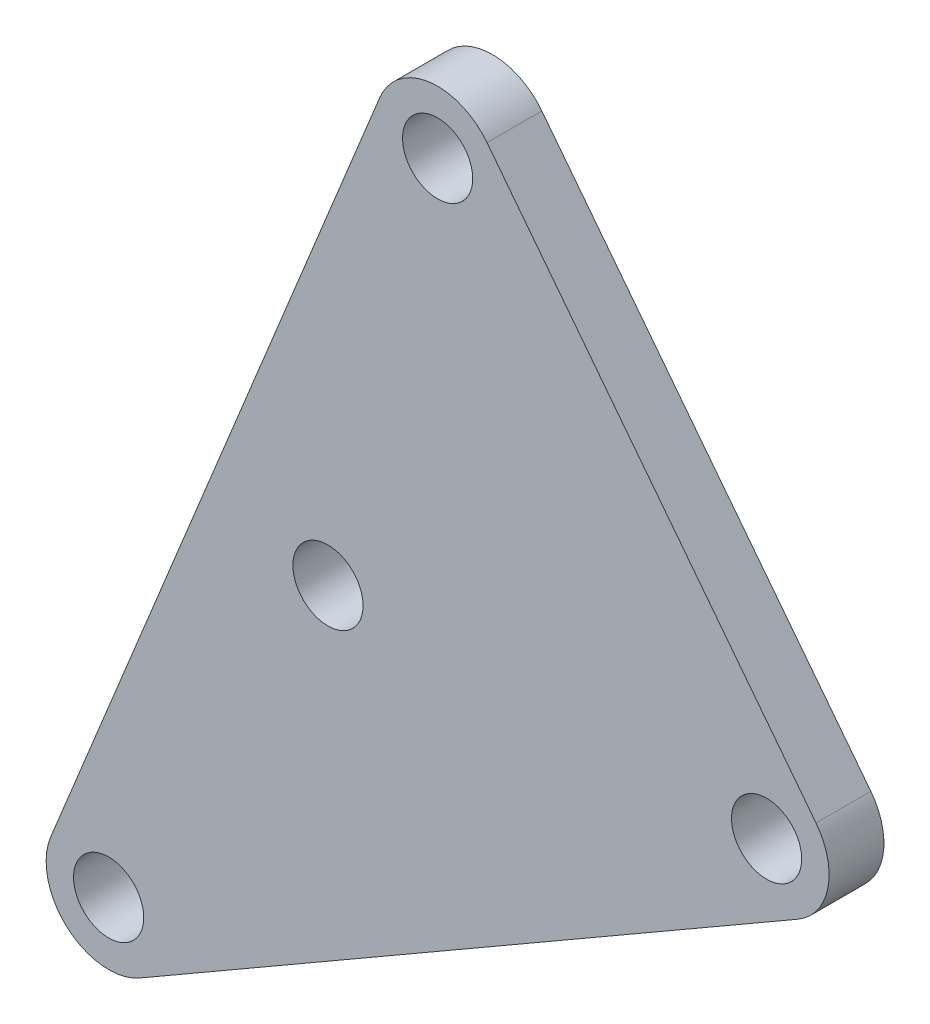
SolidWorks part; units mm, degrees
ref_plane "Front Plane" through (0, 0, 0) normal (0, 0, 1) x (1, 0, 0)
ref_plane "Top Plane" through (0, 0, 0) normal (0, 1, 0) x (1, 0, 0)
ref_plane "Right Plane" through (0, 0, 0) normal (1, 0, 0) x (0, 0, -1)
sketch "Sketch1" plane through (0, 0, 0) normal (0, 0, 1) x (1, 0, 0)
  line L3 (9.2115, 26.8099) -> (28.2615, 2.2165)
  line L6 (27.2097, -3.1346) -> (-10.8902, -25.1316)
  line L7 (2.9997, 25.9633) -> (-16.0503, -20.6272)
  circle A0 centre (0, 0) radius 2.032
  circle A1 centre (6.35, 24.5934) radius 2.032
  circle A2 centre (-12.7, -21.997) radius 2.032
  circle A3 centre (25.4, 0) radius 2.032
  arc A4 (9.2115, 26.8099) -> (2.9997, 25.9633) centre (6.35, 24.5934) ccw
  arc A5 (-16.0503, -20.6272) -> (-10.8902, -25.1316) centre (-12.7, -21.997) ccw
  arc A6 (27.2097, -3.1346) -> (28.2615, 2.2165) centre (25.4, 0) ccw
  dimension "D3" = 7.239
  dimension "D4" = 4.064
  dimension "D6" = 12.7
  dimension "D1" = 25.4
  dimension "D2" = 25.4
  dimension "D5" = 25.4
  dimension "D7" = 6.35
extrude "Boss-Extrude1" add sketch "Sketch1" along normal blind 3.175
